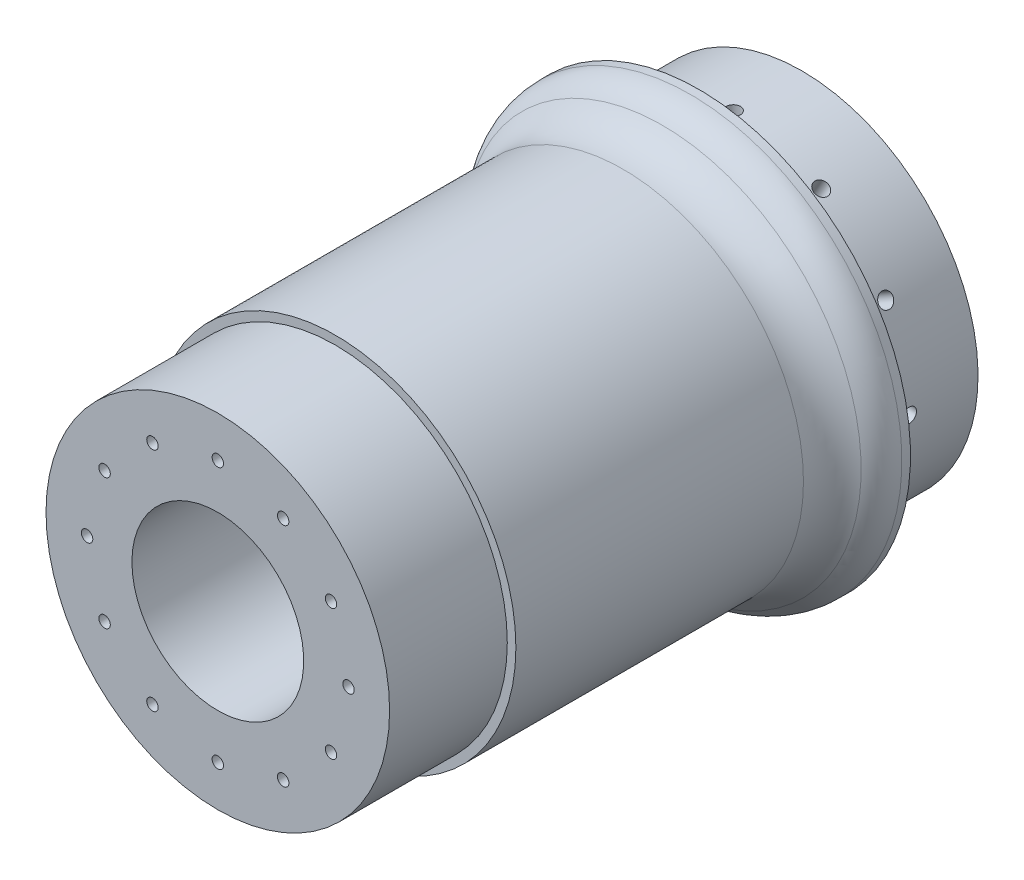
SolidWorks part; units mm, degrees
ref_plane "Front Plane" through (0, 0, 0) normal (0, 0, 1) x (1, 0, 0)
ref_plane "Top Plane" through (0, 0, 0) normal (0, 1, 0) x (1, 0, 0)
ref_plane "Right Plane" through (0, 0, 0) normal (1, 0, 0) x (0, 0, -1)
ref_plane "Plane1" through (0, 0, 0) normal (0, -1, 0) x (1, 0, 0)
sketch "Sketch1" plane through (0, 0, 0) normal (0, -1, 0) x (1, 0, 0)
  line L0 (105, -68.5) -> (0, -68.5)
  line L1 (0, -68.5) -> (0, -280)
  line L2 (0, -280) -> (123.1737, -280)
  line L5 (0, -68.5) -> (0, -280) construction
  line L6 (105, -68.5) -> (105, -235.888)
  line L8 (0, 0) -> (0, -289.5362) construction
  line L10 (123.1737, -280) -> (123.1737, -275)
  arc A3 (115.6541, -258.8169) -> (105, -235.888) centre (135, -235.888) cw
  arc A4 (123.1737, -275) -> (115.6541, -258.8169) centre (102, -275) ccw
  point P16 (108, -168.5)
revolve "Revolve1" add sketch "Sketch1" angle 360 about L5 reverse direction yes
sketch "Sketch2" plane through (0, 0, -68.5) normal (0, 0, 1) x (1, 0, 0)
  circle A0 centre (0, 0) radius 100
extrude "Boss-Extrude1" add sketch "Sketch2" along normal blind 68.5
sketch "Sketch3" plane through (0, 0, -280) normal (0, 0, -1) x (-1, 0, 0)
  circle A0 centre (0, 0) radius 102.5
extrude "Boss-Extrude2" add sketch "Sketch3" along normal blind 60
sketch "Sketch4" plane through (0, 0, 0) normal (0, -1, 0) x (1, 0, 0)
  line L0 (50, 0) -> (0, 0)
  line L1 (0, 0) -> (0, -340)
  line L2 (0, -340) -> (82.5, -340)
  line L3 (82.5, -340) -> (82.5, -153.3268)
  line L4 (50, -100) -> (50, 0)
  line L5 (0, 0) -> (0, -340) construction
  arc A0 (82.5, -153.3268) -> (66.25, -126.6634) centre (52.5, -153.3268) ccw
  arc A1 (66.25, -126.6634) -> (50, -100) centre (80, -100) cw
revolve "Cut-Revolve1" cut sketch "Sketch4" angle 360 about L5 reverse direction yes
ref_plane "Plane2" through (0, 76.0952, 0) normal (0, -1, 0) x (1, 0, 0)
sketch "Sketch5" plane through (0, 76.0952, 0) normal (0, -1, 0) x (1, 0, 0)
  line L0 (3.3235, 0) -> (0, 0)
  line L1 (0, 0) -> (0, -18)
  line L2 (0, -18) -> (3.3235, -16.003)
  line L3 (3.3235, -16.003) -> (3.3235, -12)
  line L4 (3.3235, -12) -> (3.3235, 0)
  line L5 (0, 0) -> (0, -18) construction
revolve "Cut-Revolve2" cut sketch "Sketch5" angle 360 about L5 reverse direction yes
ref_plane "Plane3" through (0, 65.9004, 0) normal (0, -1, 0) x (1, 0, 0)
sketch "Sketch6" plane through (0, 65.9004, 0) normal (0, -1, 0) x (1, 0, 0)
  line L0 (41.3711, 0) -> (38.0476, 0)
  line L1 (38.0476, 0) -> (38.0476, -18)
  line L2 (38.0476, -18) -> (41.3711, -16.003)
  line L3 (41.3711, -16.003) -> (41.3711, -12)
  line L4 (41.3711, -12) -> (41.3711, 0)
  line L5 (38.0476, 0) -> (38.0476, -18) construction
revolve "Cut-Revolve3" cut sketch "Sketch6" angle 360 about L5 reverse direction yes
ref_plane "Plane4" through (0, 38.0476, 0) normal (0, -1, 0) x (1, 0, 0)
sketch "Sketch7" plane through (0, 38.0476, 0) normal (0, -1, 0) x (1, 0, 0)
  line L0 (69.2239, 0) -> (65.9004, 0)
  line L1 (65.9004, 0) -> (65.9004, -18)
  line L2 (65.9004, -18) -> (69.2239, -16.003)
  line L3 (69.2239, -16.003) -> (69.2239, -12)
  line L4 (69.2239, -12) -> (69.2239, 0)
  line L5 (65.9004, 0) -> (65.9004, -18) construction
revolve "Cut-Revolve4" cut sketch "Sketch7" angle 360 about L5 reverse direction yes
sketch "Sketch8" plane through (0, 0, 0) normal (0, -1, 0) x (1, 0, 0)
  line L0 (79.4187, 0) -> (76.0952, 0)
  line L1 (76.0952, 0) -> (76.0952, -18)
  line L2 (76.0952, -18) -> (79.4187, -16.003)
  line L3 (79.4187, -16.003) -> (79.4187, -12)
  line L4 (79.4187, -12) -> (79.4187, 0)
  line L5 (76.0952, 0) -> (76.0952, -18) construction
revolve "Cut-Revolve5" cut sketch "Sketch8" angle 360 about L5 reverse direction yes
ref_plane "Plane5" through (0, -38.0476, 0) normal (0, -1, 0) x (1, 0, 0)
sketch "Sketch9" plane through (0, -38.0476, 0) normal (0, -1, 0) x (1, 0, 0)
  line L0 (69.2239, 0) -> (65.9004, 0)
  line L1 (65.9004, 0) -> (65.9004, -18)
  line L2 (65.9004, -18) -> (69.2239, -16.003)
  line L3 (69.2239, -16.003) -> (69.2239, -12)
  line L4 (69.2239, -12) -> (69.2239, 0)
  line L5 (65.9004, 0) -> (65.9004, -18) construction
revolve "Cut-Revolve6" cut sketch "Sketch9" angle 360 about L5 reverse direction yes
ref_plane "Plane6" through (0, -65.9004, 0) normal (0, -1, 0) x (1, 0, 0)
sketch "Sketch10" plane through (0, -65.9004, 0) normal (0, -1, 0) x (1, 0, 0)
  line L0 (41.3711, 0) -> (38.0476, 0)
  line L1 (38.0476, 0) -> (38.0476, -18)
  line L2 (38.0476, -18) -> (41.3711, -16.003)
  line L3 (41.3711, -16.003) -> (41.3711, -12)
  line L4 (41.3711, -12) -> (41.3711, 0)
  line L5 (38.0476, 0) -> (38.0476, -18) construction
revolve "Cut-Revolve7" cut sketch "Sketch10" angle 360 about L5 reverse direction yes
ref_plane "Plane7" through (0, -76.0952, 0) normal (0, -1, 0) x (1, 0, 0)
sketch "Sketch11" plane through (0, -76.0952, 0) normal (0, -1, 0) x (1, 0, 0)
  line L0 (3.3235, 0) -> (0, 0)
  line L1 (0, 0) -> (0, -18)
  line L2 (0, -18) -> (3.3235, -16.003)
  line L3 (3.3235, -16.003) -> (3.3235, -12)
  line L4 (3.3235, -12) -> (3.3235, 0)
  line L5 (0, 0) -> (0, -18) construction
revolve "Cut-Revolve8" cut sketch "Sketch11" angle 360 about L5 reverse direction yes
sketch "Sketch12" plane through (0, -65.9004, 0) normal (0, -1, 0) x (1, 0, 0)
  line L0 (-34.7241, 0) -> (-38.0476, 0)
  line L1 (-38.0476, 0) -> (-38.0476, -18)
  line L2 (-38.0476, -18) -> (-34.7241, -16.003)
  line L3 (-34.7241, -16.003) -> (-34.7241, -12)
  line L4 (-34.7241, -12) -> (-34.7241, 0)
  line L5 (-38.0476, 0) -> (-38.0476, -18) construction
revolve "Cut-Revolve9" cut sketch "Sketch12" angle 360 about L5 reverse direction yes
sketch "Sketch13" plane through (0, -38.0476, 0) normal (0, -1, 0) x (1, 0, 0)
  line L0 (-62.5769, 0) -> (-65.9004, 0)
  line L1 (-65.9004, 0) -> (-65.9004, -18)
  line L2 (-65.9004, -18) -> (-62.5769, -16.003)
  line L3 (-62.5769, -16.003) -> (-62.5769, -12)
  line L4 (-62.5769, -12) -> (-62.5769, 0)
  line L5 (-65.9004, 0) -> (-65.9004, -18) construction
revolve "Cut-Revolve10" cut sketch "Sketch13" angle 360 about L5 reverse direction yes
sketch "Sketch14" plane through (0, 0, 0) normal (0, -1, 0) x (1, 0, 0)
  line L0 (-72.7717, 0) -> (-76.0952, 0)
  line L1 (-76.0952, 0) -> (-76.0952, -18)
  line L2 (-76.0952, -18) -> (-72.7717, -16.003)
  line L3 (-72.7717, -16.003) -> (-72.7717, -12)
  line L4 (-72.7717, -12) -> (-72.7717, 0)
  line L5 (-76.0952, 0) -> (-76.0952, -18) construction
revolve "Cut-Revolve11" cut sketch "Sketch14" angle 360 about L5 reverse direction yes
sketch "Sketch15" plane through (0, 38.0476, 0) normal (0, -1, 0) x (1, 0, 0)
  line L0 (-62.5769, 0) -> (-65.9004, 0)
  line L1 (-65.9004, 0) -> (-65.9004, -18)
  line L2 (-65.9004, -18) -> (-62.5769, -16.003)
  line L3 (-62.5769, -16.003) -> (-62.5769, -12)
  line L4 (-62.5769, -12) -> (-62.5769, 0)
  line L5 (-65.9004, 0) -> (-65.9004, -18) construction
revolve "Cut-Revolve12" cut sketch "Sketch15" angle 360 about L5 reverse direction yes
sketch "Sketch16" plane through (0, 65.9004, 0) normal (0, -1, 0) x (1, 0, 0)
  line L0 (-34.7241, 0) -> (-38.0476, 0)
  line L1 (-38.0476, 0) -> (-38.0476, -18)
  line L2 (-38.0476, -18) -> (-34.7241, -16.003)
  line L3 (-34.7241, -16.003) -> (-34.7241, -12)
  line L4 (-34.7241, -12) -> (-34.7241, 0)
  line L5 (-38.0476, 0) -> (-38.0476, -18) construction
revolve "Cut-Revolve13" cut sketch "Sketch16" angle 360 about L5 reverse direction yes
ref_plane "Plane8" through (71.355, -41.1968, 0) normal (-0.866, 0.5, 0) x (0, 0, 1)
hole_wizard "Hole1" positions "Sketch18" profile "Sketch17" legacy
sketch "Sketch18" plane through (71.355, -41.1968, 0) normal (-0.866, 0.5, 0) x (0, 0, 1)
  point P0 (-300, 0)
sketch "Sketch17" plane through (71.355, -41.1968, -300) normal (0, 0, 1) x (-0.5, -0.866, 0)
  line L0 (0, 0) -> (0, 85.8648)
  line L1 (0, 85.8648) -> (4.188, 85.8648)
  line L2 (4.188, 85.8648) -> (4.188, 0)
  line L3 (4.188, 0) -> (0, 0)
  line L4 (0, 110) -> (0, -10) construction
  dimension "Diameter" = 8.376
  dimension "Depth" = 85.8648
ref_plane "Plane9" through (41.1968, -71.355, 0) normal (-0.5, 0.866, 0) x (0.866, 0.5, 0)
hole_wizard "Hole2" positions "Sketch20" profile "Sketch19" legacy
sketch "Sketch20" plane through (41.1968, -71.355, 0) normal (-0.5, 0.866, 0) x (0.866, 0.5, 0)
  point P0 (0, 300)
sketch "Sketch19" plane through (41.1968, -71.355, -300) normal (0, 0, 1) x (-0.866, -0.5, 0)
  line L0 (0, 0) -> (0, 85.8648)
  line L1 (0, 85.8648) -> (4.188, 85.8648)
  line L2 (4.188, 85.8648) -> (4.188, 0)
  line L3 (4.188, 0) -> (0, 0)
  line L4 (0, 110) -> (0, -10) construction
  dimension "Diameter" = 8.376
  dimension "Depth" = 85.8648
ref_plane "Plane10" through (0, -82.3936, 0) normal (0, 1, 0) x (1, 0, 0)
hole_wizard "Hole3" positions "Sketch22" profile "Sketch21" legacy
sketch "Sketch22" plane through (0, -82.3936, 0) normal (0, 1, 0) x (1, 0, 0)
  point P0 (0, 300)
sketch "Sketch21" plane through (0, -82.3936, -300) normal (1, 0, 0) x (0, 0, 1)
  line L0 (0, 0) -> (0, 40.7801)
  line L1 (0, 40.7801) -> (4.188, 40.7801)
  line L2 (4.188, 40.7801) -> (4.188, 0)
  line L3 (4.188, 0) -> (0, 0)
  line L4 (0, 110) -> (0, -10) construction
  dimension "Diameter" = 8.376
  dimension "Depth" = 40.7801
ref_plane "Plane11" through (-41.1968, -71.355, 0) normal (0.5, 0.866, 0) x (0.866, -0.5, 0)
hole_wizard "Hole4" positions "Sketch24" profile "Sketch23" legacy
sketch "Sketch24" plane through (-41.1968, -71.355, 0) normal (0.5, 0.866, 0) x (0.866, -0.5, 0)
  point P0 (0, 300)
sketch "Sketch23" plane through (-41.1968, -71.355, -300) normal (0, 0, 1) x (-0.866, 0.5, 0)
  line L0 (0, 0) -> (0, 85.8648)
  line L1 (0, 85.8648) -> (4.188, 85.8648)
  line L2 (4.188, 85.8648) -> (4.188, 0)
  line L3 (4.188, 0) -> (0, 0)
  line L4 (0, 110) -> (0, -10) construction
  dimension "Diameter" = 8.376
  dimension "Depth" = 85.8648
ref_plane "Plane12" through (-71.355, -41.1968, 0) normal (0.866, 0.5, 0) x (0, 0, -1)
hole_wizard "Hole5" positions "Sketch26" profile "Sketch25" legacy
sketch "Sketch26" plane through (-71.355, -41.1968, 0) normal (0.866, 0.5, 0) x (0, 0, -1)
  point P0 (300, 0)
sketch "Sketch25" plane through (-71.355, -41.1968, -300) normal (0, 0, 1) x (-0.5, 0.866, 0)
  line L0 (0, 0) -> (0, 85.8648)
  line L1 (0, 85.8648) -> (4.188, 85.8648)
  line L2 (4.188, 85.8648) -> (4.188, 0)
  line L3 (4.188, 0) -> (0, 0)
  line L4 (0, 110) -> (0, -10) construction
  dimension "Diameter" = 8.376
  dimension "Depth" = 85.8648
ref_plane "Plane13" through (-82.3936, 0, 0) normal (1, 0, 0) x (0, 0, -1)
hole_wizard "Hole6" positions "Sketch28" profile "Sketch27" legacy
sketch "Sketch28" plane through (-82.3936, 0, 0) normal (1, 0, 0) x (0, 0, -1)
  point P0 (300, 0)
sketch "Sketch27" plane through (-82.3936, 0, -300) normal (0, 1, 0) x (0, 0, -1)
  line L0 (0, 0) -> (0, 40.7801)
  line L1 (0, 40.7801) -> (4.188, 40.7801)
  line L2 (4.188, 40.7801) -> (4.188, 0)
  line L3 (4.188, 0) -> (0, 0)
  line L4 (0, 110) -> (0, -10) construction
  dimension "Diameter" = 8.376
  dimension "Depth" = 40.7801
ref_plane "Plane14" through (-71.355, 41.1968, 0) normal (0.866, -0.5, 0) x (0, 0, -1)
hole_wizard "Hole7" positions "Sketch30" profile "Sketch29" legacy
sketch "Sketch30" plane through (-71.355, 41.1968, 0) normal (0.866, -0.5, 0) x (0, 0, -1)
  point P0 (300, 0)
sketch "Sketch29" plane through (-71.355, 41.1968, -300) normal (0, 0, 1) x (0.5, 0.866, 0)
  line L0 (0, 0) -> (0, 85.8648)
  line L1 (0, 85.8648) -> (4.188, 85.8648)
  line L2 (4.188, 85.8648) -> (4.188, 0)
  line L3 (4.188, 0) -> (0, 0)
  line L4 (0, 110) -> (0, -10) construction
  dimension "Diameter" = 8.376
  dimension "Depth" = 85.8648
ref_plane "Plane15" through (-41.1968, 71.355, 0) normal (0.5, -0.866, 0) x (-0.866, -0.5, 0)
hole_wizard "Hole8" positions "Sketch32" profile "Sketch31" legacy
sketch "Sketch32" plane through (-41.1968, 71.355, 0) normal (0.5, -0.866, 0) x (-0.866, -0.5, 0)
  point P0 (0, 300)
sketch "Sketch31" plane through (-41.1968, 71.355, -300) normal (0, 0, 1) x (0.866, 0.5, 0)
  line L0 (0, 0) -> (0, 85.8648)
  line L1 (0, 85.8648) -> (4.188, 85.8648)
  line L2 (4.188, 85.8648) -> (4.188, 0)
  line L3 (4.188, 0) -> (0, 0)
  line L4 (0, 110) -> (0, -10) construction
  dimension "Diameter" = 8.376
  dimension "Depth" = 85.8648
ref_plane "Plane16" through (0, 82.3936, 0) normal (0, -1, 0) x (-1, 0, 0)
hole_wizard "Hole9" positions "Sketch34" profile "Sketch33" legacy
sketch "Sketch34" plane through (0, 82.3936, 0) normal (0, -1, 0) x (-1, 0, 0)
  point P0 (0, 300)
sketch "Sketch33" plane through (0, 82.3936, -300) normal (1, 0, 0) x (0, 0, -1)
  line L0 (0, 0) -> (0, 40.7801)
  line L1 (0, 40.7801) -> (4.188, 40.7801)
  line L2 (4.188, 40.7801) -> (4.188, 0)
  line L3 (4.188, 0) -> (0, 0)
  line L4 (0, 110) -> (0, -10) construction
  dimension "Diameter" = 8.376
  dimension "Depth" = 40.7801
ref_plane "Plane17" through (41.1968, 71.355, 0) normal (-0.5, -0.866, 0) x (-0.866, 0.5, 0)
hole_wizard "Hole10" positions "Sketch36" profile "Sketch35" legacy
sketch "Sketch36" plane through (41.1968, 71.355, 0) normal (-0.5, -0.866, 0) x (-0.866, 0.5, 0)
  point P0 (0, 300)
sketch "Sketch35" plane through (41.1968, 71.355, -300) normal (0, 0, 1) x (0.866, -0.5, 0)
  line L0 (0, 0) -> (0, 85.8648)
  line L1 (0, 85.8648) -> (4.188, 85.8648)
  line L2 (4.188, 85.8648) -> (4.188, 0)
  line L3 (4.188, 0) -> (0, 0)
  line L4 (0, 110) -> (0, -10) construction
  dimension "Diameter" = 8.376
  dimension "Depth" = 85.8648
ref_plane "Plane18" through (71.355, 41.1968, 0) normal (-0.866, -0.5, 0) x (0, 0, 1)
hole_wizard "Hole11" positions "Sketch38" profile "Sketch37" legacy
sketch "Sketch38" plane through (71.355, 41.1968, 0) normal (-0.866, -0.5, 0) x (0, 0, 1)
  point P0 (-300, 0)
sketch "Sketch37" plane through (71.355, 41.1968, -300) normal (0, 0, 1) x (0.5, -0.866, 0)
  line L0 (0, 0) -> (0, 85.8648)
  line L1 (0, 85.8648) -> (4.188, 85.8648)
  line L2 (4.188, 85.8648) -> (4.188, 0)
  line L3 (4.188, 0) -> (0, 0)
  line L4 (0, 110) -> (0, -10) construction
  dimension "Diameter" = 8.376
  dimension "Depth" = 85.8648
ref_plane "Plane19" through (82.3936, 0, 0) normal (-1, 0, 0) x (0, 0, 1)
hole_wizard "Hole12" positions "Sketch40" profile "Sketch39" legacy
sketch "Sketch40" plane through (82.3936, 0, 0) normal (-1, 0, 0) x (0, 0, 1)
  point P0 (-300, 0)
sketch "Sketch39" plane through (82.3936, 0, -300) normal (0, 1, 0) x (0, 0, 1)
  line L0 (0, 0) -> (0, 40.7801)
  line L1 (0, 40.7801) -> (4.188, 40.7801)
  line L2 (4.188, 40.7801) -> (4.188, 0)
  line L3 (4.188, 0) -> (0, 0)
  line L4 (0, 110) -> (0, -10) construction
  dimension "Diameter" = 8.376
  dimension "Depth" = 40.7801
ref_axis "Axis1" through (0, 0, -153.3268) along (0, 0, -1)
